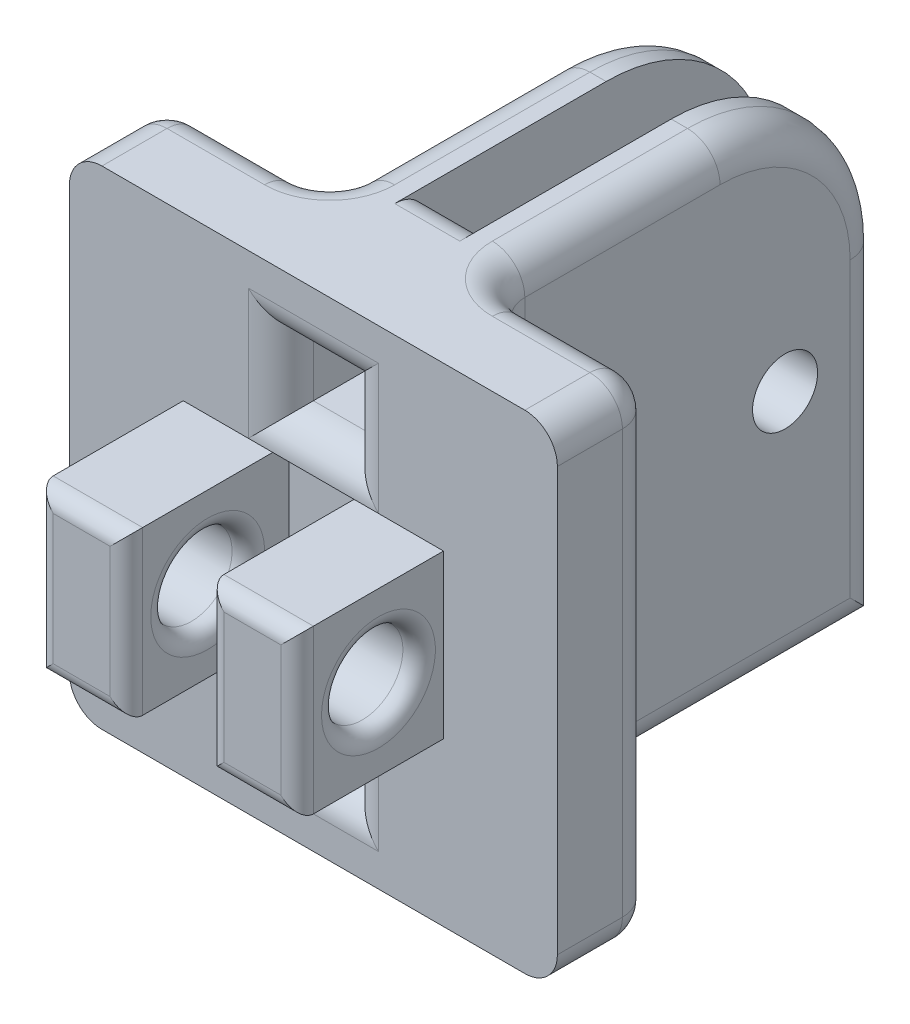
SolidWorks part; units mm, degrees
ref_plane "Front Plane" through (0, 0, 0) normal (0, 0, 1) x (1, 0, 0)
ref_plane "Top Plane" through (0, 0, 0) normal (0, 1, 0) x (1, 0, 0)
ref_plane "Right Plane" through (0, 0, 0) normal (1, 0, 0) x (0, 0, -1)
sketch "Base Sketch" plane through (0, 0, 0) normal (0, 0, 1) x (1, 0, 0)
  line L1 (-7.5, 7.5) -> (7.5, 7.5)
  line L2 (-7.5, 7.5) -> (-7.5, -7.5)
  line L3 (-7.5, -7.5) -> (7.5, -7.5)
  line L4 (7.5, 7.5) -> (7.5, -7.5)
  line L5 (-7.5, 7.5) -> (7.5, -7.5) construction
  line L6 (-7.5, -7.5) -> (7.5, 7.5) construction
  point P0 (0, 0)
  dimension "D1" = 15
  dimension "D2" = 15
extrude "Base Sketch Extrude" add sketch "Base Sketch" along normal blind 20
sketch "Nub Cutout Sketch" plane through (0, 0, 0) normal (0, 0, 1) x (1, 0, 0)
  line L0 (0, 0) -> (0, 10.3634) construction
  line L1 (7.5, 7.5) -> (-7.5, 7.5) construction
  line L2 (2.5, 7.5) -> (7.5, 7.5)
  line L3 (2.5, 7.5) -> (2.5, -7.5)
  line L4 (2.5, -7.5) -> (7.5, -7.5)
  line L5 (7.5, 7.5) -> (7.5, -7.5)
  line L6 (-2.5, -7.5) -> (-7.5, -7.5)
  line L7 (-7.5, 7.5) -> (-7.5, -7.5)
  line L8 (-2.5, 7.5) -> (-7.5, 7.5)
  line L9 (-2.5, 7.5) -> (-2.5, -7.5)
  dimension "D1" = 2.5
extrude "Nub Extruded Cut" cut sketch "Nub Cutout Sketch" along normal blind 12
sketch "Hing e Hole Sketch" plane through (7.5, 0, 0) normal (1, 0, 0) x (0, 0, -1)
  line L0 (0, 0) -> (-23.825, 0) construction
  line L1 (0, 7.5) -> (0, -7.5) construction
  circle A0 centre (-3, 0) radius 1
  dimension "D1" = 2
  dimension "D2" = 3
extrude "Hinge Hole Extruded Cut" cut sketch "Hing e Hole Sketch" against normal through all
fillet "Corner Fillets" radius 5 3 edges at (0, -7.5, 20) (0, 7.5, 20) (0, 7.5, 0)
fillet "Style Fillets" radius 1 26 edges at (-2.5, -7.5, 6) (-2.5, -2.5, 0) (-2.5, 6.0355, 1.4645) (2.5, -7.5, 6) (2.5, -2.5, 0) (2.5, 6.0355, 1.4645) (7.5, -7.5, 13.5) (7.5, -6.0355, 18.5355) (7.5, 0, 20) (7.5, 6.0355, 18.5355) (-7.5, -7.5, 13.5) (-7.5, -6.0355, 18.5355) (-7.5, 0, 20) (-7.5, 6.0355, 18.5355) (5, -7.5, 12) (7.5, 0, 12) (2.5, 0, 12) (-2.5, 7.5, 8.5) (2.5, 7.5, 8.5) (5, 7.5, 12) (7.5, 7.5, 13.5) (-7.5, 7.5, 13.5) (-5, 7.5, 12) (-7.5, 0, 12) (-5, -7.5, 12) (-2.5, 0, 12)
sketch "Routing Holes Sketch" plane through (0, 0, 0) normal (0, 0, 1) x (1, 0, 0)
  line L0 (0, 0) -> (12.7431, 0) construction
  line L1 (0, 0) -> (0, 10.48) construction
  line L2 (-6.5, 7.5) -> (6.5, 7.5) construction
  line L3 (-1, 5.5) -> (1, 5.5)
  line L4 (-1, 5.5) -> (-1, 3.5)
  line L5 (-1, 3.5) -> (1, 3.5)
  line L6 (1, 5.5) -> (1, 3.5)
  line L7 (1, -5.5) -> (1, -3.5)
  line L8 (-1, -3.5) -> (1, -3.5)
  line L9 (-1, -5.5) -> (-1, -3.5)
  line L10 (-1, -5.5) -> (1, -5.5)
  dimension "D1" = 2
  dimension "D2" = 2
  dimension "D3" = 2
extrude "Routing Holes EXtruded Cut" cut sketch "Routing Holes Sketch" along normal through all
ref_plane "CutPlane" through (0, 0, 15) normal (0, 0, 1) x (1, 0, 0)
split "Split1" trim tools "CutPlane" bodies to split 104 resulting bodies 110
sketch "Tie Down Sketch" plane through (0, 0, 0) normal (1, 0, 0) x (0, 0, -1)
  line L0 (0, 0) -> (-26.4137, 0) construction
  line L1 (-15, -6.5) -> (-15, 6.5) construction
  line L2 (-15, 2.5) -> (-19.5, 2.5)
  line L3 (-15, 2.5) -> (-15, -2.5)
  line L4 (-15, -2.5) -> (-19.5, -2.5)
  line L5 (-19.5, 2.5) -> (-19.5, -2.5)
  circle A0 centre (-17, 0) radius 1.25
  dimension "D1" = 2.5
  dimension "D4" = 2.5
  dimension "D2" = 4.5
  dimension "D3" = 5
extrude "Tie Down Extrude" add sketch "Tie Down Sketch" along normal mid plane 8
sketch "Tie Down Cutout Sketch" plane through (0, 0, 19.5) normal (0, 0, 1) x (1, 0, 0)
  line L0 (4, 2.5) -> (-4, 2.5) construction
  line L1 (-1.25, 2.5) -> (1.25, 2.5)
  line L2 (-1.25, 2.5) -> (-1.25, -2.5)
  line L3 (-1.25, -2.5) -> (1.25, -2.5)
  line L4 (1.25, 2.5) -> (1.25, -2.5)
  line L5 (4, -2.5) -> (-4, -2.5) construction
  line L6 (0, 0) -> (0, 7.7769) construction
  dimension "D1" = 2.5
extrude "Tie Down Cutout Extruded Cut" cut sketch "Tie Down Cutout Sketch" against normal blind 5
fillet "Tie Down Fillets" radius 0.5 12 edges at (-2.625, 2.5, 19.5) (-2.625, -2.5, 19.5) (2.625, -2.5, 19.5) (2.625, 2.5, 19.5) (4, 0, 15.75) (4, 0, 19.5) (1.25, 0, 19.5) (1.25, 1.25, 17) (-4, 0, 15.75) (-4, 0, 19.5) (-1.25, 0, 19.5) (-1.25, -1.25, 17)
sketch "Routing Extension Sketch" plane through (0, 7.5, 0) normal (0, 1, 0) x (1, 0, 0)
  line L1 (-1, -1) -> (1, -1)
  line L2 (-1, -1) -> (-1, -10.5)
  line L3 (-1, -10.5) -> (1, -10.5)
  line L4 (1, -1) -> (1, -10.5)
  dimension "D1" = 9.5
extrude "Routing Extension Extruded Cut" cut sketch "Routing Extension Sketch" against normal up to surface (4 mm away) up to face at (0, 3.5, 7.5505)
fillet "Routing Fillets" radius 1 12 edges at (0, 3.5, 0.101) (0, -3.5, 15) (1, -4.5, 15) (0, -5.5, 15) (-1, -4.5, 15) (0, 3.5, 15) (1, 4.5, 15) (-1, 4.5, 15) (0, 5.5, 15) (0, 7.5, 10.5) (0, -3.5, 0) (0, -5.5, 0)
